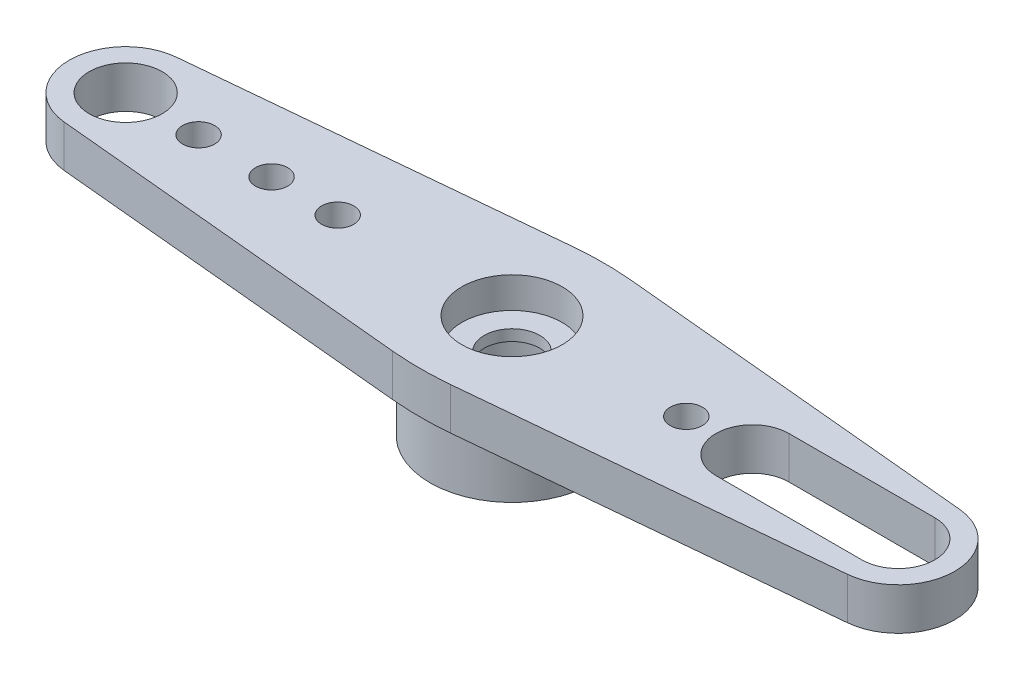
SolidWorks part; units mm, degrees
ref_plane "Front Plane" through (0, 0, 0) normal (0, 0, 1) x (1, 0, 0)
ref_plane "Top Plane" through (0, 0, 0) normal (0, 1, 0) x (1, 0, 0)
ref_plane "Right Plane" through (0, 0, 0) normal (1, 0, 0) x (0, 0, -1)
sketch "Sketch1" plane through (0, 0, 0) normal (0, 1, 0) x (1, 0, 0)
  circle A0 centre (0, 0) radius 3.3655
  circle A1 centre (0, 0) radius 2.2352
  dimension "D1" = 6.731
  dimension "D2" = 4.4704
extrude "Boss-Extrude1" add sketch "Sketch1" along normal blind 2.54
sketch "Sketch2" plane through (0, 2.54, 0) normal (0, 1, 0) x (1, 0, 0)
  line L0 (-1000, 0) -> (9.8806, 0) construction
  line L1 (0, 0) -> (0, 50000) construction
  line L2 (0, 3.8227) -> (16.0923, 2.3075)
  line L3 (0, -3.8227) -> (16.0923, -2.3075)
  line L4 (0, -3.8227) -> (-16.0923, -2.3075)
  line L5 (0, 3.8227) -> (-16.0923, 2.3075)
  line L6 (15.875, 0) -> (9.8806, 0) construction
  line L7 (15.875, -1.5) -> (9.8806, -1.5)
  line L8 (15.875, 1.5) -> (9.8806, 1.5)
  line L9 (15.875, 0) -> (50000, 0) construction
  arc A0 (15.875, -1.5) -> (15.875, 1.5) centre (15.875, 0) ccw
  arc A2 (9.8806, 1.5) -> (9.8806, -1.5) centre (9.8806, 0) ccw
  circle A3 centre (7.1628, 0) radius 0.6604
  arc A4 (14.1081, -1.5) -> (14.1081, 1.5) centre (15.875, 0) ccw
  circle A5 centre (0, 0) radius 3.8227
  circle A6 centre (-15.875, 0) radius 2.3178
  circle A7 centre (-7.1628, 0) radius 0.6604
  circle A8 centre (-9.8806, 0) radius 0.6604
  circle A9 centre (-12.8778, 0) radius 0.6604
  circle A10 centre (-15.875, 0) radius 1.5
  circle A11 centre (0, 0) radius 1.143
  arc A12 (15.875, -1.5) -> (15.875, 1.5) centre (15.875, 0) ccw
  arc A13 (9.8806, 1.5) -> (9.8806, -1.5) centre (9.8806, 0) ccw
  point P33 (12.8778, 0)
  circle M1 centre (0, 0) radius 3.3655
  circle M2 centre (0, 0) radius 2.2352
  dimension "D1" = 3
  dimension "D6" = 4.6355
  dimension "D7" = 7.6454
  dimension "D8" = 2.286
  dimension "D9" = 3
  dimension "D2" = 15.875
  dimension "D4" = 5.9944
  dimension "D5" = 8.7122
extrude "Boss-Extrude2" add sketch "Sketch2" along normal blind 1.7272 contours L5 A6 L4 A5 A8 A7 A9 | A6 A10 | A5 L3 A4 L2 A2 A3 | A4 A0 | M1 M2 | L3 A5 L2 L5 L4 M1 | A11 M2 region at (0.3466, 2.54, -3.6815) region at (8.3868, 2.54, -2.8611) region at (-8.1791, 2.54, 0) region at (18.131, 2.54, 0) region at (-14.3589, 2.54, -1.6655) region at (-3.2703, 2.54, 0) region at (-2.172, 2.54, 0)
fillet "Fillet1" radius 12.7 2 edges at (0, 3.4036, -3.8227) (0, 3.4036, 3.8227)
sketch "Sketch3" plane through (0, 4.2672, 0) normal (0, 1, 0) x (1, 0, 0)
  circle A0 centre (0, 0) radius 2.0638
  circle M17 centre (0, 0) radius 1.143
  dimension "D1" = 4.1275
extrude "Cut-Extrude1" cut sketch "Sketch3" against normal blind 1.27 contours A0 M17 region at (-2.0054, 4.2672, 0)
